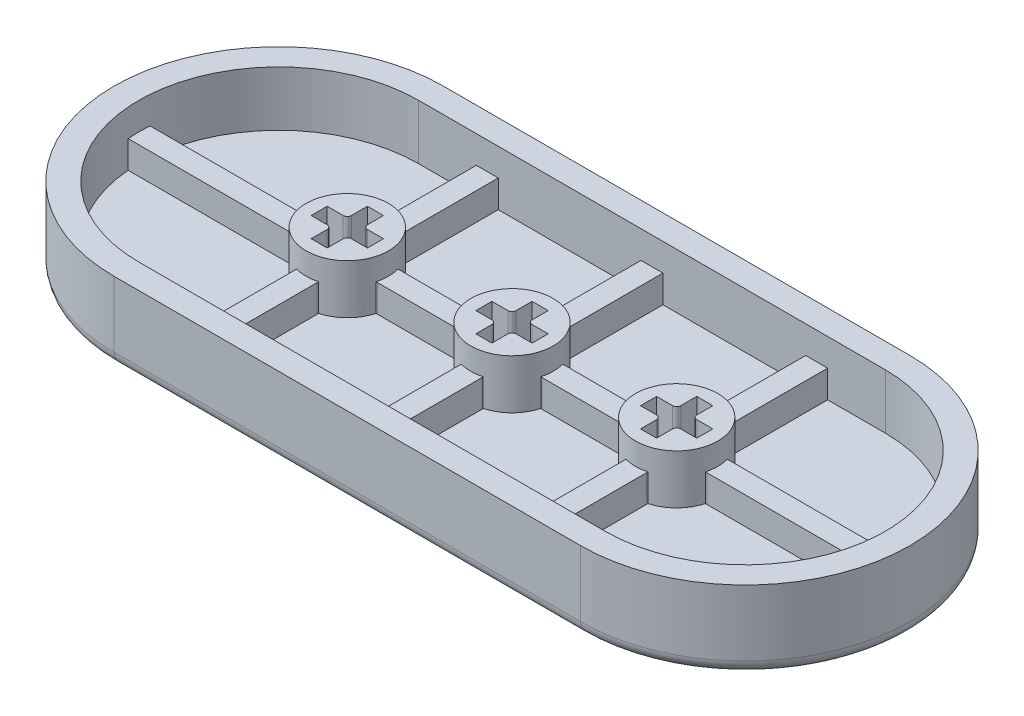
SolidWorks part; units mm, degrees
ref_plane "Front Plane" through (0, 0, 0) normal (0, 0, 1) x (1, 0, 0)
ref_plane "Top Plane" through (0, 0, 0) normal (0, 1, 0) x (1, 0, 0)
ref_plane "Right Plane" through (0, 0, 0) normal (1, 0, 0) x (0, 0, -1)
sketch "Sketch1" plane through (0, 0, 0) normal (0, 1, 0) x (1, 0, 0)
  line L0 (17, 0) -> (-17, 0) construction
  line L1 (17, -12) -> (-17, -12)
  line L2 (17, 12) -> (-17, 12)
  arc A1 (17, -12) -> (17, 12) centre (17, 0) ccw
  arc A2 (-17, 12) -> (-17, -12) centre (-17, 0) ccw
  point P5 (0, 0)
  point P10 (-29, 0)
  point P11 (29, 0)
  dimension "D2" = 12
  dimension "D3" = 58
extrude "button top" add sketch "Sketch1" along normal blind 1.8
sketch "Sketch2" plane through (0, 1.8, 0) normal (0, 1, 0) x (1, 0, 0)
  line L0 (-17, 0) -> (17, 0) construction
  line L1 (-17, 12) -> (17, 12)
  line L2 (-17, -12) -> (17, -12)
  line L3 (-17, 0) -> (17, 0) construction
  line L4 (-17, 10.2) -> (17, 10.2)
  line L5 (-17, -10.2) -> (17, -10.2)
  arc A2 (-17, 12) -> (-17, -12) centre (-17, 0) ccw
  arc A6 (17, -12) -> (17, 12) centre (17, 0) ccw
  arc A7 (17, -12) -> (17, 12) centre (17, 0) ccw construction
  arc A8 (-17, 10.2) -> (-17, -10.2) centre (-17, 0) ccw
  arc A9 (17, -10.2) -> (17, 10.2) centre (17, 0) ccw
  point P2 (0, 0)
  point P15 (0, 0)
  dimension "D1" = 1.8
extrude "button walls" add sketch "Sketch2" along normal blind 4
sketch "Sketch3" plane through (0, 1.8, 0) normal (0, 1, 0) x (1, 0, 0)
  line L0 (0, -2.05) -> (0, 2.05) construction
  line L1 (-2.05, 0) -> (2.05, 0) construction
  line L2 (-0.585, 0.885) -> (-0.585, 2.05)
  line L3 (-0.585, -2.05) -> (0.585, -2.05)
  line L4 (-0.585, -2.05) -> (-0.585, -0.885)
  line L5 (-0.585, 2.05) -> (0.585, 2.05)
  line L6 (0.585, -2.05) -> (0.585, -0.885)
  line L7 (-0.585, -2.05) -> (0.585, 2.05) construction
  line L8 (-0.585, 2.05) -> (0.585, -2.05) construction
  line L9 (-2.05, -0.585) -> (-0.885, -0.585)
  line L10 (-2.05, -0.585) -> (-2.05, 0.585)
  line L11 (-2.05, 0.585) -> (-0.885, 0.585)
  line L12 (2.05, -0.585) -> (2.05, 0.585)
  line L13 (-2.05, -0.585) -> (2.05, 0.585) construction
  line L14 (-2.05, 0.585) -> (2.05, -0.585) construction
  line L15 (0.885, 0.585) -> (2.05, 0.585)
  line L16 (0.585, 0.885) -> (0.585, 2.05)
  line L17 (0.885, -0.585) -> (2.05, -0.585)
  line L18 (11.415, 0.885) -> (11.415, 2.05)
  line L19 (11.415, -2.05) -> (12.585, -2.05)
  line L20 (11.415, -2.05) -> (11.415, -0.885)
  line L21 (11.415, 2.05) -> (12.585, 2.05)
  line L22 (12.585, -2.05) -> (12.585, -0.885)
  line L23 (9.95, -0.585) -> (11.115, -0.585)
  line L24 (9.95, -0.585) -> (9.95, 0.585)
  line L25 (9.95, 0.585) -> (11.115, 0.585)
  line L26 (14.05, -0.585) -> (14.05, 0.585)
  line L27 (12.885, 0.585) -> (14.05, 0.585)
  line L28 (12.585, 0.885) -> (12.585, 2.05)
  line L29 (12.885, -0.585) -> (14.05, -0.585)
  line L30 (12, -2.05) -> (12, 2.05) construction
  line L31 (9.95, 0) -> (14.05, 0) construction
  line L32 (11.415, -2.05) -> (12.585, 2.05) construction
  line L33 (11.415, 2.05) -> (12.585, -2.05) construction
  line L34 (9.95, -0.585) -> (14.05, 0.585) construction
  line L35 (9.95, 0.585) -> (14.05, -0.585) construction
  line L36 (-12.585, 0.885) -> (-12.585, 2.05)
  line L37 (-12.585, -2.05) -> (-11.415, -2.05)
  line L38 (-12.585, -2.05) -> (-12.585, -0.885)
  line L39 (-12.585, 2.05) -> (-11.415, 2.05)
  line L40 (-11.415, -2.05) -> (-11.415, -0.885)
  line L41 (-14.05, -0.585) -> (-12.885, -0.585)
  line L42 (-14.05, -0.585) -> (-14.05, 0.585)
  line L43 (-14.05, 0.585) -> (-12.885, 0.585)
  line L44 (-9.95, -0.585) -> (-9.95, 0.585)
  line L45 (-11.115, 0.585) -> (-9.95, 0.585)
  line L46 (-11.415, 0.885) -> (-11.415, 2.05)
  line L47 (-11.115, -0.585) -> (-9.95, -0.585)
  line L48 (-12, -2.05) -> (-12, 2.05) construction
  line L49 (-14.05, 0) -> (-9.95, 0) construction
  line L50 (-12.585, -2.05) -> (-11.415, 2.05) construction
  line L51 (-12.585, 2.05) -> (-11.415, -2.05) construction
  line L52 (-14.05, -0.585) -> (-9.95, 0.585) construction
  line L53 (-14.05, 0.585) -> (-9.95, -0.585) construction
  circle A0 centre (0, 0) radius 3
  arc A1 (-0.585, -0.885) -> (-0.885, -0.585) centre (-0.885, -0.885) ccw
  arc A2 (0.585, -0.885) -> (0.885, -0.585) centre (0.885, -0.885) cw
  arc A3 (0.885, 0.585) -> (0.585, 0.885) centre (0.885, 0.885) cw
  arc A4 (-0.585, 0.885) -> (-0.885, 0.585) centre (-0.885, 0.885) cw
  circle A5 centre (12, 0) radius 3
  arc A6 (11.415, -0.885) -> (11.115, -0.585) centre (11.115, -0.885) ccw
  arc A7 (12.585, -0.885) -> (12.885, -0.585) centre (12.885, -0.885) cw
  arc A8 (12.885, 0.585) -> (12.585, 0.885) centre (12.885, 0.885) cw
  arc A9 (11.415, 0.885) -> (11.115, 0.585) centre (11.115, 0.885) cw
  circle A10 centre (-12, 0) radius 3
  arc A11 (-12.585, -0.885) -> (-12.885, -0.585) centre (-12.885, -0.885) ccw
  arc A12 (-11.415, -0.885) -> (-11.115, -0.585) centre (-11.115, -0.885) cw
  arc A13 (-11.115, 0.585) -> (-11.415, 0.885) centre (-11.115, 0.885) cw
  arc A14 (-12.585, 0.885) -> (-12.885, 0.585) centre (-12.885, 0.885) cw
  point P6 (0, 0)
  point P9 (0, 0)
  point P22 (2.05, 0)
  point P24 (0, 2.05)
  point P29 (0.585, -0.585)
  point P32 (0.585, 0.585)
  point P40 (12, 0)
  point P43 (12, 0)
  point P69 (-12, 0)
  point P72 (-12, 0)
  dimension "D1" = 6
  dimension "D4" = 0.3
  dimension "D2" = 4.1
  dimension "D3" = 1.17
  dimension "D5" = 2
  dimension "D6" = 2
extrude "stem housing" add sketch "Sketch3" along normal blind 3.6
sketch "Sketch4" plane through (0, 1.8, 0) normal (0, 1, 0) x (1, 0, 0)
  line L0 (0, 3) -> (0, 10.2) construction
  line L1 (-0.8, 3) -> (-0.8, 10.2)
  line L2 (0.8, 3) -> (0.8, 10.2)
  line L3 (0, -3.19) -> (0, 3.19) construction
  line L6 (-15, 0) -> (-27.2, 0) construction
  line L9 (9, 0) -> (3, 0) construction
  line L12 (9, 0.8) -> (3, 0.8)
  line L15 (9, -0.8) -> (3, -0.8)
  line L18 (15, 0) -> (27.2, 0) construction
  line L19 (15, -0.8) -> (27.2, -0.8)
  line L20 (15, 0.8) -> (27.2, 0.8)
  line L21 (12, 3) -> (12, 10.2) construction
  line L22 (11.2, 3) -> (11.2, 10.2)
  line L23 (12.8, 3) -> (12.8, 10.2)
  line L24 (-12, 3) -> (-12, 10.2) construction
  line L25 (-12.8, 3) -> (-12.8, 10.2)
  line L26 (-11.2, 3) -> (-11.2, 10.2)
  line L27 (-15, -0.8) -> (-27.2, -0.8)
  line L28 (-15, 0.8) -> (-27.2, 0.8)
  line L29 (-3.19, 0) -> (3.19, 0) construction
  line L32 (-9, 0) -> (-3, 0) construction
  line L33 (-9, 0.8) -> (-3, 0.8)
  line L34 (-9, -0.8) -> (-3, -0.8)
  line L35 (0, -3) -> (0, -10.2) construction
  line L36 (-0.8, -3) -> (-0.8, -10.2)
  line L37 (0.8, -3) -> (0.8, -10.2)
  line L38 (12, -3) -> (12, -10.2) construction
  line L39 (11.2, -3) -> (11.2, -10.2)
  line L40 (12.8, -3) -> (12.8, -10.2)
  line L41 (-12, -3) -> (-12, -10.2) construction
  line L42 (-12.8, -3) -> (-12.8, -10.2)
  line L43 (-11.2, -3) -> (-11.2, -10.2)
  line L44 (17, 10.2) -> (-17, 10.2) construction
  circle A0 centre (0, 0) radius 3 construction
  circle A1 centre (0, 0) radius 3 construction
  arc A3 (-0.8, 3) -> (0.8, 3) centre (0, 3) ccw
  arc A4 (0.8, 10.2) -> (-0.8, 10.2) centre (0, 10.2) ccw
  arc A15 (9, 0.8) -> (9, -0.8) centre (9, 0) cw
  arc A16 (3, -0.8) -> (3, 0.8) centre (3, 0) cw
  arc A17 (15, -0.8) -> (15, 0.8) centre (15, 0) cw
  arc A18 (27.2, 0.8) -> (27.2, -0.8) centre (27.2, 0) cw
  arc A19 (11.2, 3) -> (12.8, 3) centre (12, 3) ccw
  arc A20 (12.8, 10.2) -> (11.2, 10.2) centre (12, 10.2) ccw
  arc A21 (-12.8, 3) -> (-11.2, 3) centre (-12, 3) ccw
  arc A22 (-11.2, 10.2) -> (-12.8, 10.2) centre (-12, 10.2) ccw
  circle A23 centre (-12, 0) radius 3 construction
  circle A24 centre (-12, 0) radius 3 construction
  arc A25 (-17, 10.2) -> (-17, -10.2) centre (-17, 0) ccw construction
  arc A26 (-15, -0.8) -> (-15, 0.8) centre (-15, 0) ccw
  arc A27 (-27.2, 0.8) -> (-27.2, -0.8) centre (-27.2, 0) ccw
  arc A33 (-9, 0.8) -> (-9, -0.8) centre (-9, 0) ccw
  arc A34 (-3, -0.8) -> (-3, 0.8) centre (-3, 0) ccw
  arc A35 (-0.8, -3) -> (0.8, -3) centre (0, -3) cw
  arc A36 (0.8, -10.2) -> (-0.8, -10.2) centre (0, -10.2) cw
  arc A37 (11.2, -3) -> (12.8, -3) centre (12, -3) cw
  arc A38 (12.8, -10.2) -> (11.2, -10.2) centre (12, -10.2) cw
  arc A39 (-12.8, -3) -> (-11.2, -3) centre (-12, -3) cw
  arc A40 (-11.2, -10.2) -> (-12.8, -10.2) centre (-12, -10.2) cw
  point P6 (0, 0)
  point P7 (-14.6632, 7.5768)
  point P9 (0, 6.6)
  point P19 (6, 0)
  point P33 (21.1, 0)
  point P40 (12, 6.6)
  point P47 (-12, 6.6)
  point P55 (0, -6.6)
  point P59 (-21.1, 0)
  point P69 (12, -6.6)
  point P76 (-12, -6.6)
  point P81 (-6, 0)
  point P93 (0, 0)
  dimension "D1" = 1.6
  dimension "D3" = 2
  dimension "D4" = 12
  dimension "D5" = 12
  dimension "D2" = 2
extrude "Boss-Extrude4" add sketch "Sketch4" along normal blind 2
fillet "Fillet1" radius 1 4 edges at (0, 0, -12) (-29, 0, 0) (0, 0, 12) (29, 0, 0)
